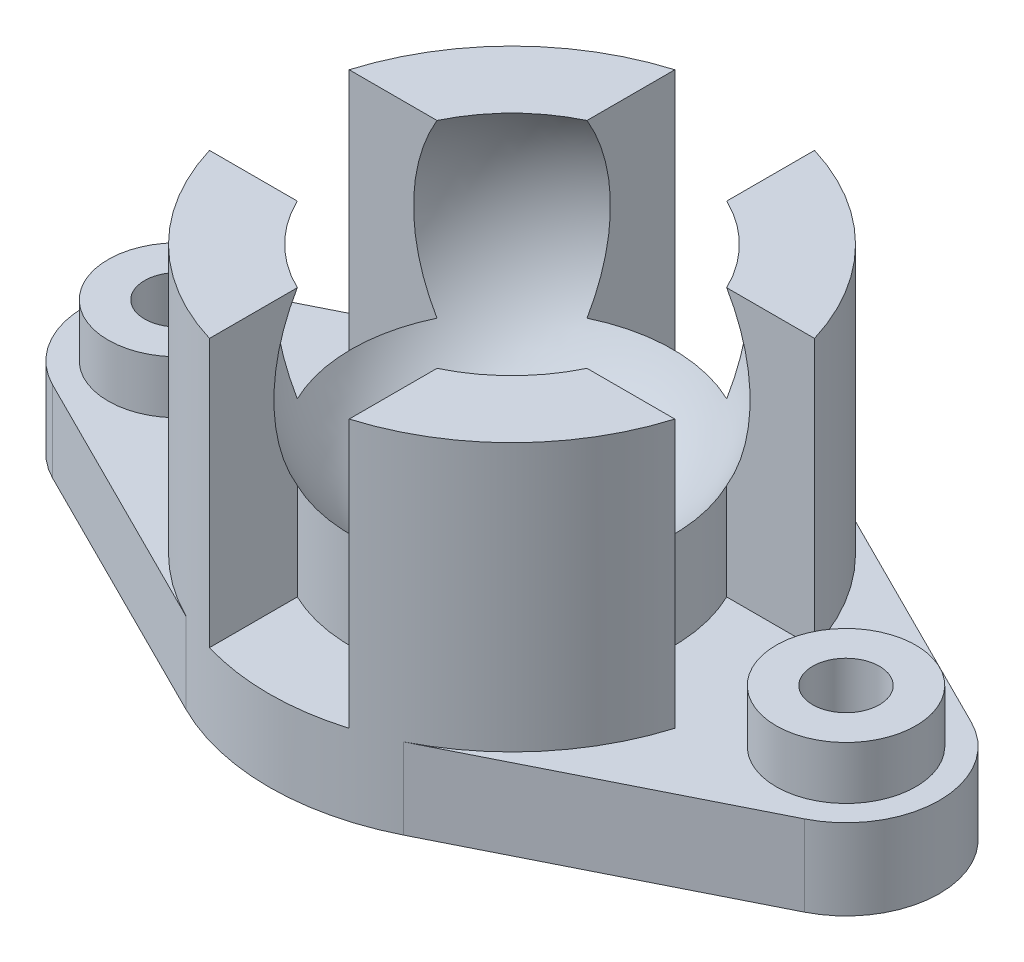
SolidWorks part; units mm, degrees
material "Plastique personnalisé"
ref_plane "Plan de face" through (0, 0, 0) normal (0, 0, 1) x (1, 0, 0)
ref_plane "Plan de dessus" through (0, 0, 0) normal (0, 1, 0) x (1, 0, 0)
ref_plane "Plan de droite" through (0, 0, 0) normal (1, 0, 0) x (0, 0, -1)
sketch "Esquisse1" plane through (0, 0, 0) normal (0, 1, 0) x (1, 0, 0)
  line L0 (0, 0) -> (-18.6257, 0) construction
  line L1 (0, 0) -> (18.3125, 0) construction
  line L2 (0, 0) -> (0, 12.3421) construction
  line L3 (-12.3771, 2.7517) -> (-3.5803, 7.1541)
  line L4 (-12.3771, -2.7517) -> (-3.5803, -7.1541)
  line L5 (-12.3771, 2.7517) -> (-3.5803, 7.1541)
  line L6 (-12.3771, -2.7517) -> (-3.5803, -7.1541)
  line L7 (12.3771, -2.7517) -> (3.5803, -7.1541)
  line L8 (12.3771, 2.7517) -> (3.5803, 7.1541)
  line L9 (12.3771, -2.7517) -> (3.5803, -7.1541)
  line L10 (12.3771, 2.7517) -> (3.5803, 7.1541)
  circle A0 centre (0, 0) radius 8
  arc A3 (-12.3771, 2.7517) -> (-12.3771, -2.7517) centre (-11, 0) ccw
  circle A4 centre (-11, 0) radius 2.3
  circle A5 centre (11, 0) radius 2.3
  arc A6 (12.3771, 2.7517) -> (12.3771, -2.7517) centre (11, 0) cw
  dimension "D1" = 16
  dimension "D3" = 11
extrude "Boss.-Extru.1" add sketch "Esquisse1" along normal blind 2.66 contours L3 A3 L4 A0 A4 | A6 L8 A0 L7 A5 | A0 | A4 | A5 region at (-7.8993, 0, -4.7942) region at (0, 0, 0) region at (7.8993, 0, -4.7942) region at (-11, 0, 0) region at (11, 0, 0)
extrude "Boss.-Extru.2" add sketch "Esquisse1<3>" along normal blind 4.4 contours A4 | A5 region at (-11, 0, 0) region at (11, 0, 0)
sketch "Esquisse1<3>" plane through (0, 0, 0) normal (0, 1, 0) x (1, 0, 0) same geometry as "Esquisse1"
extrude "Boss.-Extru.3" add sketch "Esquisse1<4>" along normal blind 11.48 contours A0 region at (0, 0, 0)
sketch "Esquisse1<4>" plane through (0, 0, 0) normal (0, 1, 0) x (1, 0, 0) same geometry as "Esquisse1"
sketch "Esquisse2" plane through (0, 0, 0) normal (0, 0, 1) x (1, 0, 0)
  line L0 (8, 2.66) -> (-7.9787, 2.66) construction
  line L1 (8, 2.66) -> (3.5803, 2.66) construction
  line L2 (-12.3771, 2.66) -> (-3.5803, 2.66) construction
  line L3 (0, 2.66) -> (0, 14.66)
  arc A0 (0, 14.66) -> (0, 2.66) centre (0, 8.66) ccw
  dimension "D1" = 12
ref_axis "Axe1" through (0, -0.733, 0) along (0, 1, 0)
revolve "Enlèvement de matière-Révolution7" cut sketch "Esquisse2" angle 360 about axis through (0, -0.733, 0) along (0, 1, 0) region at (-2.5465, 8.66, 0)
sketch "Esquisse3" plane through (0, 11.48, 0) normal (0, 1, 0) x (1, 0, 0)
  line L0 (-8.5909, 2.3) -> (8.6194, 2.3)
  line L2 (8.6194, -2.3) -> (-8.5909, -2.3)
  line L4 (-2.3, 0) -> (-2.3, 9.1474)
  line L5 (-2.3, 9.1474) -> (2.3, 9.1474)
  line L6 (2.3, 9.1474) -> (2.3, -8.8906)
  line L7 (2.3, -8.8906) -> (-2.3, -8.8906)
  line L8 (-2.3, -8.8906) -> (-2.3, 2.0978)
  line L9 (-8.5909, -2.3) -> (-8.5909, 2.3)
  line L10 (8.6194, -2.3) -> (8.6194, 2.3)
  circle M4 centre (0, 0) radius 5.296
  circle M5 centre (0, 0) radius 8
  dimension "D1" = 4.6
  dimension "D2" = 2.3
extrude "Enlèv. mat.-Extru.1" cut sketch "Esquisse3" against normal blind 8.82 contours L6 L4 M5 M4 | L2 L0 M5 M4 | L8 L6 M5 M4 | L2 L0 M4 M5 region at (-6.5039, 11.48, 0) region at (0, 11.48, -6.5039) region at (0, 11.48, 6.5039) region at (6.5039, 11.48, 0)
hole_wizard "Dégagement M22" positions "Esquisse3D3" profile "Esquisse6" hole size "M2" standard "ISO" end condition through all
sketch3d "Esquisse3D3"
  line L0 (11, 4.4, 0) -> (11, 2.66, 0) construction
  line L1 (-11, 4.4, 0) -> (-11, 2.66, 0) construction
  point P0 (11, 4.4, 0)
  point P4 (-11, 4.4, 0)
sketch "Esquisse6" plane through (11, 4.4, 0) normal (1, 0, 0) x (0, 0, 1)
  line L0 (0, 0) -> (0, 4.4)
  line L1 (0, 4.4) -> (1.1, 4.4)
  line L2 (1.1, 4.4) -> (1.1, 0)
  line L5 (1.1, 0) -> (0, 0)
  line L11 (0, -6.35) -> (0, 107.95) construction
  dimension "Diamètre du perçage jusqu'au prochain" = 2.2
  dimension "Profondeur du perçage jusqu'au prochain" = 4.4
